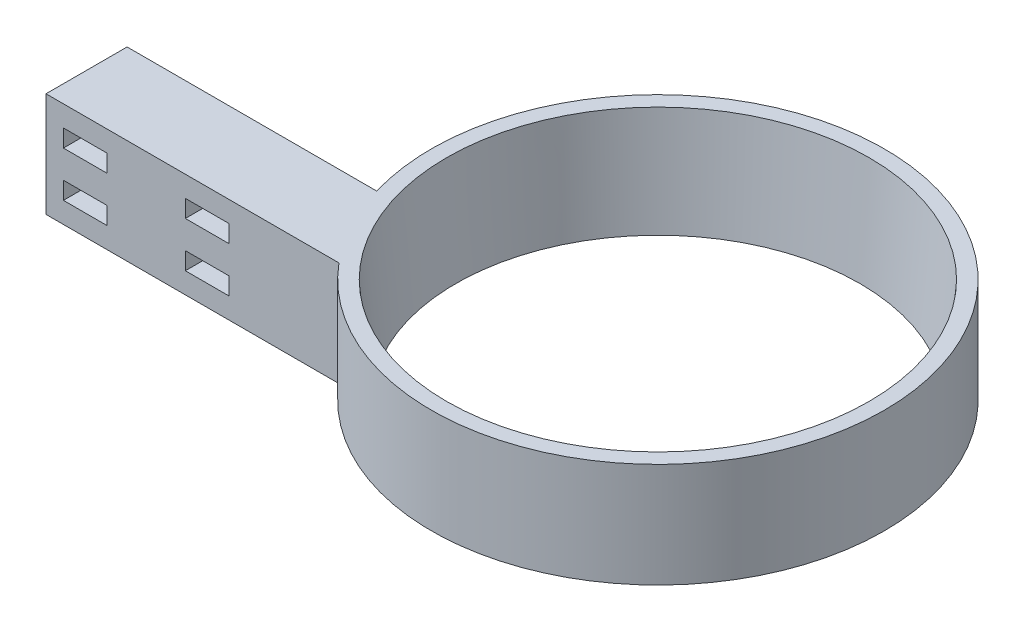
SolidWorks part; units mm, degrees
ref_plane "Front Plane" through (0, 0, 0) normal (0, 0, 1) x (1, 0, 0)
ref_plane "Top Plane" through (0, 0, 0) normal (0, 1, 0) x (1, 0, 0)
ref_plane "Right Plane" through (0, 0, 0) normal (1, 0, 0) x (0, 0, -1)
sketch "Sketch1" plane through (0, 0, 0) normal (0, 1, 0) x (1, 0, 0)
  line L0 (0, 0) -> (-41.275, 0) construction
  circle A0 centre (0, 0) radius 41.275
  dimension "D1" = 82.55
extrude "Outer Circle" add sketch "Sketch1" along normal blind 19.05 contours A0
ref_plane "Connector Midplane" through (0, 0, 19.05) normal (0, 0, 1) x (1, 0, 0)
sketch "Sketch3" plane through (0, 0, 0) normal (0, -1, 0) x (1, 0, 0)
  line L0 (0, 0) -> (-41.275, 0) construction
  line L1 (-31.6935, 26.4414) -> (-85.09, 26.4414)
  line L2 (-85.09, 26.4414) -> (-85.09, 11.6586)
  line L3 (-85.09, 11.6586) -> (-39.5942, 11.6586)
  line L4 (10.4775, 19.05) -> (-10.4775, 19.05) construction
  circle A0 centre (0, 0) radius 41.275 construction
  arc A1 (-39.5942, 11.6586) -> (-31.6935, 26.4414) centre (0, 0) cw
  point P7 (-85.09, 19.05)
  dimension "D1" = 14.7828
  dimension "D2" = 43.815
extrude "Connector" add sketch "Sketch3" against normal blind 3.175 contours L3 A1 L1 L2
sketch "Sketch4" plane through (0, 0, 26.4414) normal (0, 0, 1) x (1, 0, 0)
  line L0 (-85.09, 3.175) -> (-85.09, 19.05)
  line L1 (-85.09, 19.05) -> (-31.6935, 19.05)
  line L2 (41.275, 19.05) -> (-41.275, 19.05) construction
  line L3 (-31.6935, 19.05) -> (-31.6935, 3.175)
  line L4 (-31.6935, 3.175) -> (-85.09, 3.175) construction
  line L5 (-31.6935, 3.175) -> (-85.09, 3.175)
  line L6 (-31.6935, 3.175) -> (-39.5942, 3.175) construction
  line L7 (-31.6935, 3.175) -> (-31.6935, 0) construction
sketch "Sketch5" plane through (0, 0, 11.6586) normal (0, 0, -1) x (-1, 0, 0)
  line L0 (85.09, 3.175) -> (85.09, 19.05)
  line L1 (85.09, 19.05) -> (31.6935, 19.05)
  line L2 (31.6935, 19.05) -> (31.6935, 3.175)
  line L3 (31.6935, 3.175) -> (85.09, 3.175)
  line L4 (41.275, 19.05) -> (-41.275, 19.05) construction
extrude "Outside Wall" add sketch "Sketch4" against normal blind 3.175
extrude "Inside Wall" add sketch "Sketch5" against normal up to surface (11.6078 mm away) up to face at (-59.5913, 11.1125, 23.2664)
sketch "Sketch2" plane through (0, 0, 0) normal (0, -1, 0) x (1, 0, 0)
  circle A0 centre (0, 0) radius 36.83
  dimension "D1" = 73.66
extrude "Cup Cut" cut sketch "Sketch2" against normal through all draft 5 draft outward yes
sketch "Sketch7" plane through (0, 0, 26.4414) normal (0, 0, 1) x (1, 0, 0)
  line L0 (-85.09, 9.525) -> (-31.6935, 9.525) construction
  line L1 (-85.09, 19.05) -> (-85.09, 0) construction
  line L2 (-31.6935, 19.05) -> (-31.6935, 0) construction
  line L4 (-31.6935, 19.05) -> (-85.09, 19.05) construction
  line L7 (-81.915, 15.24) -> (-73.9775, 15.24)
  line L8 (-81.915, 15.24) -> (-81.915, 12.065)
  line L9 (-81.915, 12.065) -> (-73.9775, 12.065)
  line L10 (-73.9775, 15.24) -> (-73.9775, 12.065)
  line L11 (-81.915, 15.24) -> (-73.9775, 12.065) construction
  line L12 (-81.915, 12.065) -> (-73.9775, 15.24) construction
  point P12 (-77.9462, 13.6525)
  dimension "D1" = 3.175
  dimension "D2" = 7.9375
  dimension "D3" = 9.525
  dimension "D4" = 3.81
  dimension "D5" = 3.175
extrude "Slot" cut sketch "Sketch7" against normal up to next
ref_plane "Plane2" through (0, 9.525, 0) normal (0, 1, 0) x (1, 0, 0)
pattern_linear "LPattern1" count 2 spacing 22.225 along (1, 0, 0) of "Slot"
mirror "Mirror2" about plane through (0, 9.525, 0) normal (0, 1, 0) of "LPattern1"
sketch "Sketch8" plane through (0, 0, 26.4414) normal (0, 0, 1) x (1, 0, 0)
  line L0 (-85.09, 9.525) -> (-50.3371, 9.525) construction
  line L1 (-85.09, 19.05) -> (-85.09, 0) construction
  line L2 (-81.915, 15.24) -> (-73.9775, 12.065) construction
  line L3 (-73.9775, 15.24) -> (-81.915, 15.24) construction
  line L4 (-81.915, 15.24) -> (-81.915, 12.065) construction
  line L5 (-73.9775, 15.24) -> (-81.915, 12.065) construction
  point P16 (-77.9462, 13.6525)
  dimension "D1" = 4.1275
  dimension "D2" = 7.1438
sketch "Sketch6" plane through (0, 19.05, 0) normal (0, 1, 0) x (1, 0, 0)
  line L0 (-85.09, -11.6586) -> (-85.09, -26.4414) construction
  line L1 (-85.09, -20.5486) -> (-78.74, -20.5486)
  line L2 (-85.09, -20.5486) -> (-85.09, -17.5514)
  line L3 (-85.09, -17.5514) -> (-78.74, -17.5514)
  line L4 (-78.74, -20.5486) -> (-78.74, -17.5514)
  line L5 (-72.39, -20.5486) -> (-72.39, -17.5514)
  line L6 (-72.39, -20.5486) -> (-66.04, -20.5486)
  line L7 (-66.04, -20.5486) -> (-66.04, -17.5514)
  line L8 (-72.39, -17.5514) -> (-66.04, -17.5514)
  line L9 (-59.69, -20.5486) -> (-59.69, -17.5514)
  line L10 (-59.69, -20.5486) -> (-53.34, -20.5486)
  line L11 (-53.34, -20.5486) -> (-53.34, -17.5514)
  line L12 (-59.69, -17.5514) -> (-53.34, -17.5514)
  line L13 (-10.4775, -19.05) -> (10.4775, -19.05) construction
  line L14 (-59.69, -17.5514) -> (-53.34, -17.5514)
  line L15 (-53.34, -17.5514) -> (-53.34, -20.5486)
  line L16 (-59.69, -20.5486) -> (-53.34, -20.5486)
  line L17 (-59.69, -17.5514) -> (-59.69, -20.5486)
  line L18 (-72.39, -17.5514) -> (-66.04, -17.5514)
  line L19 (-66.04, -17.5514) -> (-66.04, -20.5486)
  line L20 (-72.39, -20.5486) -> (-66.04, -20.5486)
  line L21 (-72.39, -17.5514) -> (-72.39, -20.5486)
  line L22 (-85.09, -20.5486) -> (-78.74, -20.5486)
  line L23 (-78.74, -17.5514) -> (-78.74, -20.5486)
  line L24 (-85.09, -17.5514) -> (-78.74, -17.5514)
  line L25 (-85.09, -17.5514) -> (-85.09, -20.5486)
  point P6 (-85.09, -19.05)
  point P7 (-85.09, -19.05)
  dimension "D1" = 2.9972
  dimension "D2" = 6.35
  dimension "D3" = 3
  dimension "D4" = 6.35
extrude "Boss-Extrude5" add sketch "Sketch6" along normal blind 3.429 rebuild error yes
fillet "Fillet1" radius 0.508 rebuild error yes
mirror "Mirror1" about plane through (0, 9.525, 0) normal (0, 1, 0) rebuild error yes
ref_plane "Plane3" through (0, 0, -50.8) normal (0, 0, 1) x (1, 0, 0)
